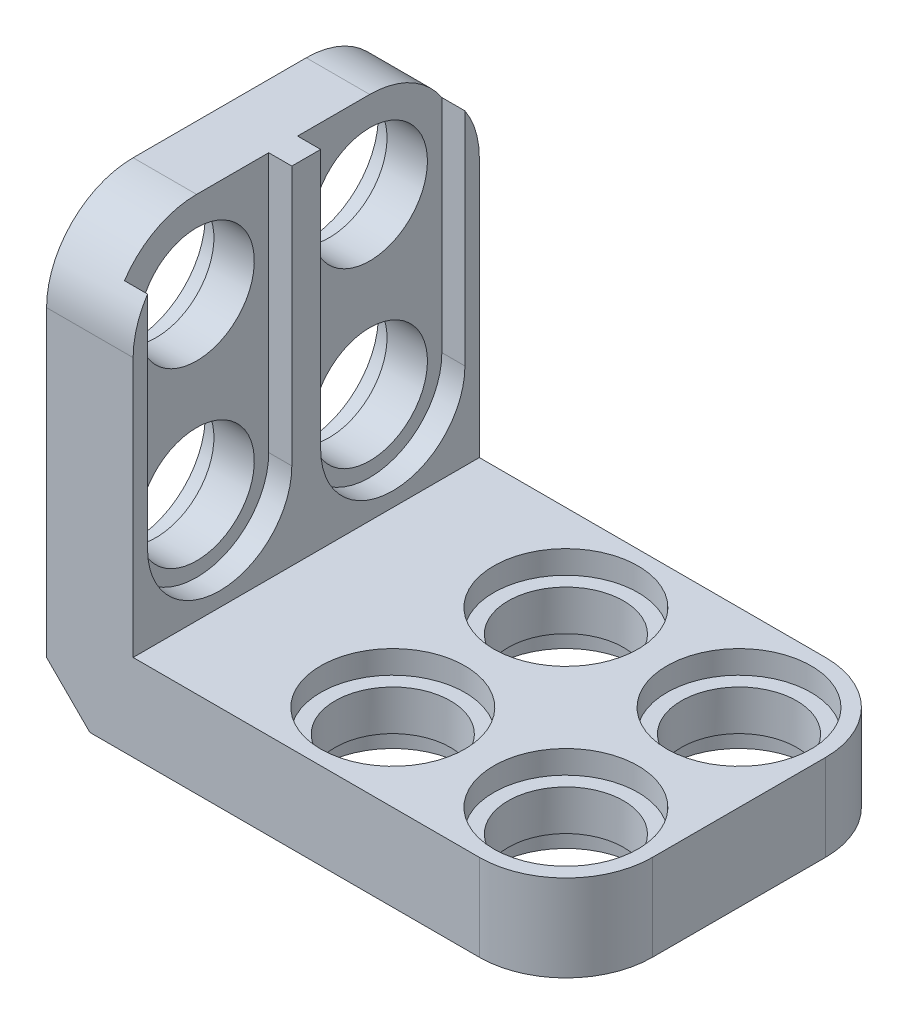
SolidWorks part; units mm, degrees
material "ABS"
ref_plane "Front Plane" through (0, 0, 0) normal (0, 0, 1) x (1, 0, 0)
ref_plane "Top Plane" through (0, 0, 0) normal (0, 1, 0) x (1, 0, 0)
ref_plane "Right Plane" through (0, 0, 0) normal (1, 0, 0) x (0, 0, -1)
sketch "Sketch1" plane through (0, 0, 0) normal (0, 0, 1) x (1, 0, 0)
  line L0 (0, 7.5) -> (0, -7.5)
  line L1 (0, -7.5) -> (18, -7.5)
  line L2 (18, -7.5) -> (18, -4.5)
  line L3 (18, -4.5) -> (3, -4.5)
  line L4 (3, -4.5) -> (3, 7.5)
  line L5 (3, 7.5) -> (0, 7.5)
  dimension "D1" = 3
  dimension "D2" = 15
  dimension "D3" = 3
  dimension "D4" = 18
extrude "Boss-Extrude1" add sketch "Sketch1" along normal mid plane 12
hole_wizard "Hole2" positions "Sketch7" profile "Sketch8" legacy end condition through all
sketch "Sketch7" plane through (0, -4.5, 0) normal (0, 1, 0) x (1, 0, 0)
  line L0 (3, -6) -> (3, 6) construction
  line L1 (18, 6) -> (3, 6) construction
  line L2 (18, -6) -> (3, -6) construction
  point P0 (15, 3)
  point P2 (9, 3)
  point P4 (9, -3)
  point P6 (15, -3)
  dimension "D1" = 6
  dimension "D2" = 6
  dimension "D3" = 6
  dimension "D4" = 6
  dimension "D5" = 3
  dimension "D6" = 3
sketch "Sketch8" plane through (15, -4.5, -3) normal (1, 0, 0) x (0, 0, 1)
  line L0 (0, 0) -> (0, 4.2017)
  line L1 (0, 4.2017) -> (2, 3)
  line L2 (2, 3) -> (2, 0.8)
  line L3 (2, 0.8) -> (2.5, 0.8)
  line L4 (2.5, 0) -> (0, 0)
  line L5 (0, -11.3109) -> (0, 121.1557) construction
  line L6 (0, 4.2017) -> (-2, 3) construction
  line L7 (2.5, 0.8) -> (2.5, 0)
  dimension "Depth" = 3
  dimension "Drill Angle" = 118
  dimension "Diameter" = 4
  dimension "C-Bore Diameter" = 5
  dimension "C-Bore Depth" = 0.8
hole_wizard "Hole3" positions "Sketch9" profile "Sketch10" legacy end condition through all
sketch "Sketch9" plane through (0, 0, 0) normal (-1, 0, 0) x (0, 0, 1)
  line L1 (6, 7.5) -> (-6, 7.5) construction
  line L2 (6, 7.5) -> (6, -7.5) construction
  point P0 (3, -1.5)
  point P2 (-3, -1.5)
  point P4 (3, 4.5)
  point P6 (-3, 4.5)
  dimension "D1" = 6
  dimension "D2" = 6
  dimension "D3" = 9
  dimension "D4" = 3
sketch "Sketch10" plane through (0, -1.5, 3) normal (0, 1, 0) x (0, 0, 1)
  line L0 (0, 0) -> (0, 19.2017)
  line L1 (0, 19.2017) -> (2, 18)
  line L2 (2, 18) -> (2, 0.8)
  line L3 (2, 0.8) -> (2.5, 0.8)
  line L4 (2.5, 0) -> (0, 0)
  line L5 (0, -11.3109) -> (0, 121.1557) construction
  line L6 (0, 19.2017) -> (-2, 18) construction
  line L7 (2.5, 0.8) -> (2.5, 0)
  dimension "Depth" = 18
  dimension "Drill Angle" = 118
  dimension "Diameter" = 4
  dimension "C-Bore Diameter" = 5
  dimension "C-Bore Depth" = 0.8
sketch "Sketch11" plane through (3, 0, 0) normal (1, 0, 0) x (0, 0, -1)
  line L0 (-6, 7.5) -> (6, 7.5) construction
  line L2 (5.5, -1.5) -> (5.5, 7.5)
  line L3 (5.5, 7.5) -> (0.5, 7.5)
  line L4 (0.5, -1.5) -> (0.5, 7.5)
  arc A0 (0.5, -1.5) -> (5.5, -1.5) centre (3, -1.5) ccw
  dimension "D1" = 5
  dimension "D2" = 5
extrude "Cut-Extrude1" cut sketch "Sketch11" against normal blind 0.8
sketch "Sketch12" plane through (0, -7.5, 0) normal (0, -1, 0) x (-1, 0, 0)
  line L0 (0, 6) -> (-18, 6) construction
  line L1 (-3, 0.5) -> (0, 0.5)
  line L2 (-3, 5.5) -> (0, 5.5)
  line L3 (0, -6) -> (0, 6) construction
  line L4 (0, 5.5) -> (0, 0.5)
  arc A0 (-3, 5.5) -> (-3, 0.5) centre (-3, 3) ccw
  circle A1 centre (-9, 3) radius 2 construction
  circle A2 centre (-9, 3) radius 2.5
  circle A3 centre (-15, 3) radius 2.5
  dimension "D1" = 5
  dimension "D3" = 3
  dimension "D4" = 5
  dimension "D5" = 5
  dimension "D2" = 6
  dimension "D6" = 3
extrude "Cut-Extrude2" cut sketch "Sketch12" against normal blind 0.8
sketch "Sketch14" plane through (0, 0, 0) normal (-1, 0, 0) x (0, 0, 1)
  line L1 (-6, 7.5) -> (-6, -7.5) construction
  line L4 (6, -7.5) -> (-0.5, -7.5) construction
  circle A0 centre (-3, -7.5) radius 2.35
  dimension "D1" = 4.7
  dimension "D2" = 3
extrude "Cut-Extrude3" cut sketch "Sketch14" against normal blind 0.8
mirror "Mirror1" about plane through (0, 0, 0) normal (0, 0, 1) of "Cut-Extrude1", "Cut-Extrude2", "Cut-Extrude3"
chamfer "Chamfer1" distance 1.5 angle 45 3 edges at (0, -7.5, 5.75) (0, -7.5, 0) (0, -7.5, -5.75)
fillet "Fillet1" radius 3 4 edges at (18, -6, 6) (18, -6, -6) (1.5, 7.5, 6) (1.5, 7.5, -6)
